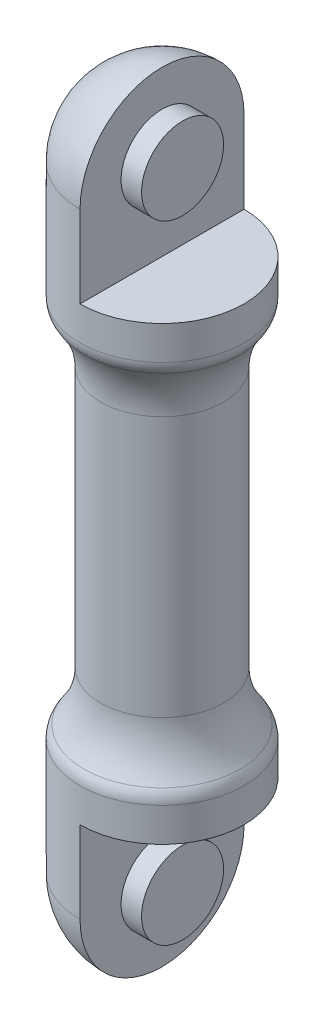
SolidWorks part; units mm, degrees
ref_plane "Front Plane" through (0, 0, 0) normal (0, 0, 1) x (1, 0, 0)
ref_plane "Top Plane" through (0, 0, 0) normal (0, 1, 0) x (1, 0, 0)
ref_plane "Right Plane" through (0, 0, 0) normal (1, 0, 0) x (0, 0, -1)
sketch "Sketch1" plane through (0, 0, 0) normal (0, 1, 0) x (1, 0, 0)
  circle A0 centre (0, 0) radius 40
extrude "Boss-Extrude1" add sketch "Sketch1" along normal blind 100
sketch "Sketch3" plane through (0, 100, 0) normal (0, 1, 0) x (1, 0, 0)
  circle A0 centre (0, 0) radius 30
extrude "Boss-Extrude2" add sketch "Sketch3" along normal blind 180
sketch "Sketch4" plane through (0, 280, 0) normal (0, 1, 0) x (1, 0, 0)
  circle A0 centre (0, 0) radius 40
extrude "Boss-Extrude3" add sketch "Sketch4" along normal blind 100
sketch "Sketch5" plane through (0, 380, 0) normal (0, 1, 0) x (1, 0, 0)
  line L0 (0, 41.0006) -> (0, -40.5161)
  line L1 (0, 41.0006) -> (41.2428, 41.0006)
  line L2 (0, -40.5161) -> (41.2428, -40.5161)
  line L3 (41.2428, 41.0006) -> (41.2428, -40.5161)
extrude "Cut-Extrude1" cut sketch "Sketch5" against normal blind 80
sketch "Sketch6" plane through (0, 0, 0) normal (0, -1, 0) x (1, 0, 0)
  line L0 (0, 40.6899) -> (0, -40.8246)
  line L1 (0, 40.6899) -> (41.9621, 40.6899)
  line L2 (0, -40.8246) -> (41.9621, -40.8246)
  line L3 (41.9621, 40.6899) -> (41.9621, -40.8246)
extrude "Cut-Extrude2" cut sketch "Sketch6" against normal blind 80
fillet "Fillet3" radius 40 1 edges at (-40, 0, 0)
fillet "Fillet4" radius 40 1 edges at (-40, 380, 0)
sketch "Sketch7" plane through (0, 0, 0) normal (1, 0, 0) x (0, 0, -1)
  circle A0 centre (0, 36.361) radius 20
extrude "Boss-Extrude4" add sketch "Sketch7" along normal blind 10
sketch "Sketch8" plane through (0, 0, 0) normal (1, 0, 0) x (0, 0, -1)
  circle A0 centre (0, 342.2831) radius 20
extrude "Boss-Extrude5" add sketch "Sketch8" along normal blind 10
fillet "Fillet5" radius 40 1 edges at (0, 100, 30)
fillet "Fillet6" radius 40 1 edges at (0, 280, 30)
fillet "Fillet7" radius 10 1 edges at (0, 280, 40)
fillet "Fillet8" radius 10 1 edges at (0, 100, 40)
